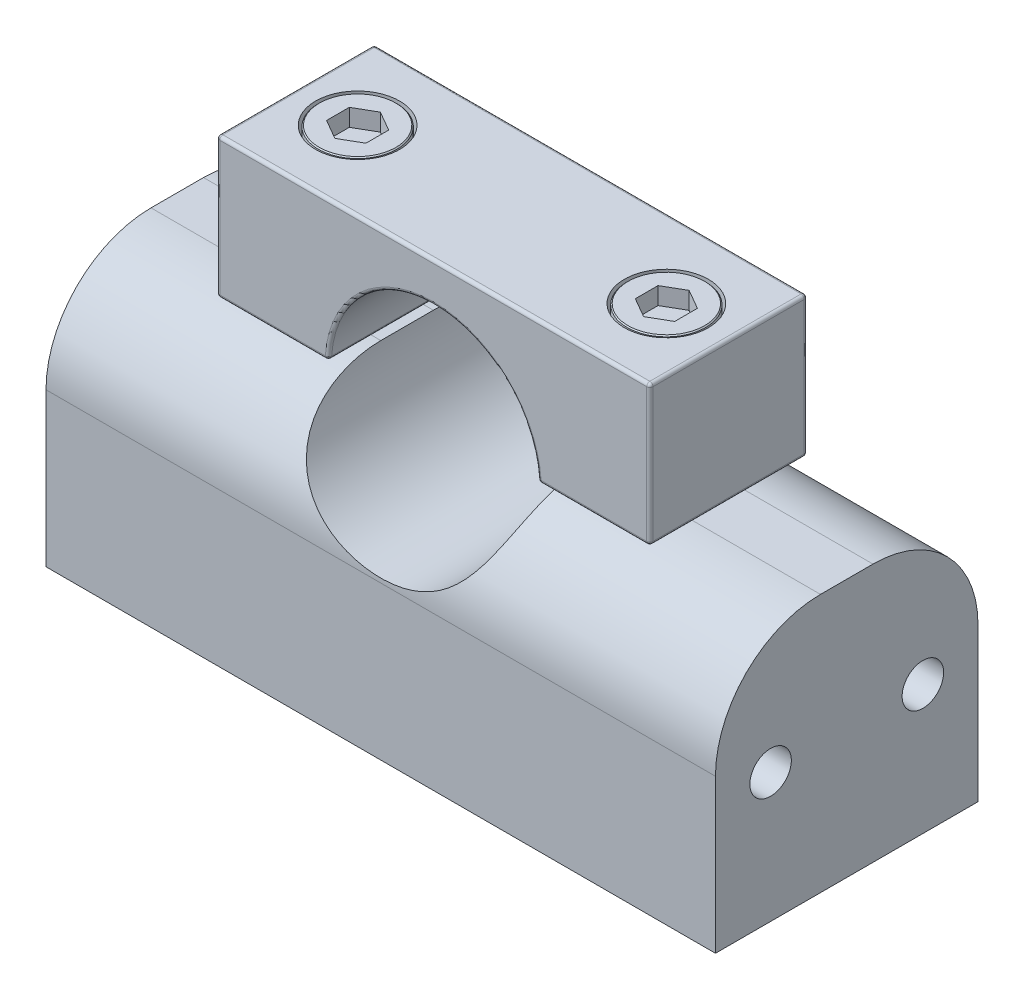
SolidWorks part; units mm, degrees
ref_plane "Front" through (0, 0, 0) normal (0, 0, 1) x (1, 0, 0)
ref_plane "Top" through (0, 0, 0) normal (0, 1, 0) x (1, 0, 0)
ref_plane "Right" through (0, 0, 0) normal (1, 0, 0) x (0, 0, -1)
sketch "Sketch1" plane through (0, 0, 0) normal (0, 0, 1) x (1, 0, 0)
  line L0 (0, 49.2125) -> (0, 0) construction
  line L1 (-40.4812, 0) -> (40.4812, 0) construction
  line L2 (0, 0) -> (0, 31.75) construction
  line L3 (-33.3375, 0) -> (33.3375, 0) construction
  line L4 (29.7815, 0) -> (36.8935, 0) construction
  line L5 (36.8935, 0) -> (36.8935, 1.27) construction
  line L6 (29.7815, 0) -> (29.7815, 1.27) construction
  line L7 (-29.7815, 0) -> (-29.7815, 1.27) construction
  line L8 (-36.8935, 0) -> (-36.8935, 1.27) construction
  line L9 (-29.7815, 0) -> (-36.8935, 0) construction
  line L10 (-26.1938, 31.75) -> (26.1938, 31.75) construction
  line L11 (-26.1937, 31.242) -> (26.1937, 31.242) construction
  line L12 (-26.1937, 32.258) -> (26.1937, 32.258) construction
  line L13 (29.4005, 0) -> (29.4005, 1.27) construction
  line L14 (37.2745, 0) -> (37.2745, 1.27) construction
  line L15 (-29.4005, 0) -> (-29.4005, 1.27) construction
  line L16 (-37.2745, 0) -> (-37.2745, 1.27) construction
  line L17 (-11.0713, 31.242) -> (11.0713, 31.242) construction
  line L18 (-11.0713, 32.258) -> (11.0713, 32.258) construction
  line L19 (-11.0713, 31.75) -> (11.0713, 31.75) construction
  line L20 (-40.4812, 0) -> (-40.4812, 9.8425) construction
  line L21 (-40.4812, 9.8425) -> (-26.1938, 9.8425) construction
  line L22 (-26.1937, 31.242) -> (-26.1938, 9.8425) construction
  line L23 (-26.1937, 32.258) -> (-26.1937, 49.2125) construction
  line L24 (-26.1937, 49.2125) -> (26.1937, 49.2125) construction
  line L25 (40.4812, 0) -> (40.4812, 9.8425) construction
  line L26 (40.4812, 9.8425) -> (26.1938, 9.8425) construction
  line L27 (26.1937, 31.242) -> (26.1938, 9.8425) construction
  line L28 (26.1937, 32.258) -> (26.1937, 49.2125) construction
  line L29 (0, 49.2125) -> (0, 42.8625) construction
  line L30 (0.3175, 42.8625) -> (-0.3175, 42.8625) construction
  line L31 (26.1938, 9.8425) -> (26.1938, 0) construction
  line L32 (-33.3375, 0) -> (-33.3375, 9.8425) construction
  line L33 (0, 44.45) -> (26.1937, 44.45) construction
  line L34 (0, 24.6062) -> (26.1937, 24.6062) construction
  circle A0 centre (0, 31.75) radius 12.7 construction
  arc A1 (-28.0988, 9.8425) -> (-26.1937, 11.7475) centre (-28.0988, 11.7475) ccw construction
  arc A2 (28.0988, 9.8425) -> (26.1937, 11.7475) centre (28.0988, 11.7475) cw construction
  point P5 (0, 0)
  point P9 (0, 31.75)
  point P11 (0, 0)
  point P12 (33.3375, 0)
  point P13 (-33.3375, 0)
  point P16 (33.3375, 0)
  point P37 (0, 31.242)
  point P40 (0, 32.258)
  point P60 (0, 42.8625)
  point P64 (33.3375, 9.8425)
  dimension "D1" = 1.27
  dimension "D8" = 9.8425
  dimension "D12" = 0.635
  dimension "D10" = 1.905
  dimension "D11" = 1.905
  dimension "D9" = 7.1437
  dimension "D3" = 0.508
  dimension "D4" = 0.381
  dimension "D5" = 0.381
  dimension "D6" = 0.381
  dimension "D7" = 0.381
sketch "Sketch3" plane through (0, 0, 0) normal (0, 0, 1) x (1, 0, 0)
  line L0 (-26.1937, 49.2125) -> (26.1937, 49.2125) construction
  line L1 (26.1937, 32.258) -> (26.1937, 49.2125) construction
  line L2 (-26.1937, 32.258) -> (26.1937, 32.258) construction
  line L3 (-26.1937, 32.258) -> (-26.1937, 49.2125) construction
  line L6 (-40.4812, 0) -> (-40.4812, 9.8425) construction
  line L7 (-40.4812, 0) -> (40.4812, 0) construction
  line L8 (40.4812, 0) -> (40.4812, 9.8425) construction
  line L11 (-26.1937, 31.242) -> (26.1937, 31.242) construction
  line L12 (-26.1937, 49.2125) -> (26.1937, 49.2125)
  line L13 (26.1937, 32.258) -> (26.1937, 49.2125)
  line L14 (-26.1937, 32.258) -> (-12.6898, 32.258)
  line L15 (-26.1937, 32.258) -> (-26.1937, 49.2125)
  line L18 (-40.4812, 0) -> (-40.4812, 9.8425)
  line L19 (-40.4812, 0) -> (40.4812, 0)
  line L20 (40.4812, 0) -> (40.4812, 9.8425)
  line L23 (-26.1937, 31.242) -> (-12.6898, 31.242)
  line L24 (12.6898, 32.258) -> (26.1937, 32.258)
  line L25 (12.6898, 31.242) -> (26.1937, 31.242)
  line L26 (-40.4812, 9.8425) -> (-40.4812, 31.242)
  line L27 (-40.4812, 31.242) -> (-26.1937, 31.242)
  line L28 (40.4812, 9.8425) -> (40.4812, 31.242)
  line L29 (40.4812, 31.242) -> (26.1937, 31.242)
  circle A2 centre (0, 31.75) radius 12.7 construction
  arc A5 (12.6898, 32.258) -> (-12.6898, 32.258) centre (0, 31.75) ccw
  arc A6 (-12.6898, 31.242) -> (12.6898, 31.242) centre (0, 31.75) ccw
extrude "Boss-Extrude1" add sketch "Sketch3" against normal blind 19.05
sketch "Sketch4" plane through (0, 0, 0) normal (0, -1, 0) x (1, 0, 0)
  line L0 (-40.4813, 0) -> (-40.4812, -19.05) construction
  line L1 (-40.4812, 0) -> (-26.1937, 0) construction
  line L2 (-40.4812, -9.525) -> (40.4812, -9.525) construction
  line L3 (40.4812, -19.05) -> (40.4812, 0) construction
  line L4 (-33.3375, 0) -> (-33.3375, -19.05) construction
  line L5 (33.3375, 0) -> (33.3375, -19.05) construction
  line L6 (-40.4812, -19.05) -> (40.4812, -19.05) construction
  line L7 (0, 0) -> (0, -19.05) construction
  circle A0 centre (-33.3375, -9.525) radius 3.556
  circle A1 centre (33.3375, -9.525) radius 3.556
  point P7 (-40.4812, -9.525)
  dimension "D1" = 7.112
sketch "Sketch6" plane through (0, 9.8425, 0) normal (0, 1, 0) x (1, 0, 0)
  line L0 (0, 0) -> (0, 19.05) construction
  line L1 (-40.4813, 0) -> (40.4812, 0) construction
  line L2 (26.1937, 19.05) -> (-26.1937, 19.05) construction
  circle A1 centre (-33.3375, 9.525) radius 3.556 construction
  circle A2 centre (-33.3375, 9.525) radius 3.556
  circle A4 centre (-33.3375, 9.525) radius 3.937
  circle A5 centre (33.3375, 9.525) radius 3.937
  dimension "D1" = 0.381
sketch "Sketch7" plane through (0, 0, 0) normal (0, 0, 1) x (1, 0, 0)
  line L0 (-40.4812, 9.5885) -> (40.4812, 9.5885) construction
  line L1 (-26.1937, 31.242) -> (-26.1937, 0) construction
  line L2 (-40.4812, 0) -> (40.4812, 0) construction
  line L3 (26.1937, 31.242) -> (26.1937, 0) construction
  line L5 (-40.4812, 0) -> (-40.4812, 9.8425) construction
  line L6 (-40.4812, 9.8425) -> (-26.1938, 9.8425) construction
  line L7 (40.4812, 0) -> (40.4812, 9.8425) construction
  line L8 (-33.3375, 9.8425) -> (-33.3375, 9.5885) construction
  line L9 (33.3375, 9.8425) -> (33.3375, 9.5885) construction
  line L10 (40.4812, 9.8425) -> (26.1938, 9.8425) construction
  dimension "D1" = 0.254
sketch "Sketch8" plane through (0, 31.242, 0) normal (0, 1, 0) x (1, 0, 0)
  line L0 (0, 0) -> (0, 19.05) construction
  line L1 (26.1938, 19.05) -> (-26.1937, 19.05) construction
  circle A0 centre (-33.3375, 9.525) radius 3.937 construction
  circle A1 centre (33.3375, 9.525) radius 3.937 construction
  circle A2 centre (-33.3375, 9.525) radius 3.937 construction
  circle A3 centre (33.3375, 9.525) radius 3.937 construction
  circle A4 centre (-33.3375, 9.525) radius 4.318
  circle A5 centre (33.3375, 9.525) radius 4.318
  dimension "CounterBoreID" = 8.636
sketch "Sketch10" plane through (0, 49.2125, 0) normal (0, 1, 0) x (1, 0, 0)
  line L0 (-26.1937, 19.05) -> (-26.1937, 0) construction
  line L1 (26.1937, 19.05) -> (26.1937, 0) construction
  line L2 (-26.1937, 19.05) -> (-26.1937, 0) construction
  line L3 (26.1937, 19.05) -> (26.1937, 0) construction
  line L4 (-23.4315, 19.05) -> (-23.4315, 0) construction
  line L5 (0, 0) -> (0, 19.05) construction
  line L6 (23.4315, 19.05) -> (23.4315, 0) construction
  circle A0 centre (-18.669, 9.525) radius 3.175 construction
  circle A1 centre (18.669, 9.525) radius 3.429
  circle A2 centre (-18.669, 9.525) radius 3.429
  circle A3 centre (18.669, 9.525) radius 3.175 construction
  circle A4 centre (-18.669, 9.525) radius 4.7625 construction
  circle A5 centre (18.669, 9.525) radius 4.7625 construction
extrude "Cut-Extrude4" cut sketch "Sketch10" against normal through all
ref_plane "Plane1" through (0, 0, -9.525) normal (0, 0, 1) x (1, 0, 0)
sketch "Sketch12" plane through (0, 49.2125, 0) normal (0, 1, 0) x (1, 0, 0)
  line L0 (0, 19.05) -> (0, 0) construction
  circle A0 centre (-18.669, 9.525) radius 4.953 construction
  circle A1 centre (18.669, 9.525) radius 5.08
  circle A2 centre (-18.669, 9.525) radius 5.08
  circle A3 centre (18.669, 9.525) radius 4.953 construction
  dimension "D2" = 10.16
  dimension "D1" = 0.127
extrude "Cut-Extrude5" cut sketch "Sketch12" against normal blind 6.731
sketch "Sketch13" plane through (0, 0, 0) normal (0, 1, 0) x (1, 0, 0)
  line L0 (-18.669, 19.05) -> (-18.669, 0) construction
  line L1 (26.1937, 19.05) -> (-26.1937, 19.05) construction
  line L2 (0, 19.05) -> (0, 0) construction
  line L3 (18.669, 19.05) -> (18.669, 0) construction
  circle A0 centre (-18.669, 9.525) radius 2.0066 construction
  point P2 (-18.669, 9.525)
  point P9 (-18.669, 19.05)
  point P10 (-18.669, 0)
  point P17 (18.669, 19.05)
  point P18 (18.669, 0)
  dimension "D1" = 4.0132
sketch "Sketch15" plane through (0, 0, -9.525) normal (0, 0, 1) x (1, 0, 0)
  line L0 (-18.669, 19.685) -> (-18.669, 49.2125) construction
  line L1 (-18.669, 49.2125) -> (-23.4315, 49.2125) construction
  line L2 (-23.4315, 49.2125) -> (-23.4315, 42.8625) construction
  line L3 (-23.4315, 42.8625) -> (-21.844, 42.8625) construction
  line L4 (-21.844, 42.8625) -> (-21.844, 19.685) construction
  line L5 (-21.844, 19.685) -> (-18.669, 19.685) construction
  line L8 (-26.1937, 49.2125) -> (26.1937, 49.2125) construction
  line L9 (-18.669, 19.685) -> (-18.669, 49.2125)
  line L10 (-18.669, 49.2125) -> (-23.4315, 49.2125)
  line L11 (-23.4315, 49.2125) -> (-23.4315, 42.8625)
  line L12 (-23.4315, 42.8625) -> (-21.844, 42.8625)
  line L13 (-21.844, 42.8625) -> (-21.844, 19.685)
  line L14 (-21.844, 19.685) -> (-18.669, 19.685)
  dimension "D2" = 4.7625
  dimension "D1" = 6.35
  dimension "D3" = 3.175
  dimension "Screw Length" = 29.5275
revolve "Revolve1" add sketch "Sketch15" angle 360 about L9
chamfer "Chamfer1" distance 0.127 angle 45 1 edges at (-18.669, 49.2125, -14.2875)
sketch "Sketch16" plane through (0, 49.2125, 0) normal (0, 1, 0) x (1, 0, 0)
  line L0 (-18.669, 19.05) -> (-18.669, 0) construction
  line L1 (-18.669, 12.2746) -> (-21.0502, 10.8998)
  line L2 (-21.0502, 10.8998) -> (-21.0502, 8.1502)
  line L3 (-21.0502, 8.1502) -> (-18.669, 6.7754)
  line L4 (-18.669, 6.7754) -> (-16.2877, 8.1502)
  line L5 (-16.2877, 8.1502) -> (-16.2877, 10.8998)
  line L6 (-16.2877, 10.8998) -> (-18.669, 12.2746)
  circle A0 centre (-18.669, 9.525) radius 2.3813 construction
  dimension "Hex Size" = 4.7625
extrude "Cut-Extrude6" cut sketch "Sketch16" against normal blind 2.0955
mirror "Mirror1" about plane through (0, 0, 0) normal (1, 0, 0) of bodies 121 119
fillet "Fillet1" radius 0.381 18 edges at (0, 49.2125, -19.05) (-26.1937, 49.2125, -9.525) (-26.1937, 40.7353, -19.05) (-26.1937, 40.7353, 0) (26.1937, 40.7353, -19.05) (26.1937, 49.2125, -9.525) (26.1937, 40.7353, 0) (0, 49.2125, 0) (26.1937, 32.258, -9.525) (19.4418, 32.258, -19.05) (-19.4418, 32.258, -19.05) (-26.1937, 32.258, -9.525) (-19.4418, 32.258, 0) (19.4418, 32.258, 0) (0, 44.45, -19.05) (0, 44.45, 0) (12.6898, 32.258, -9.525) (-12.6898, 32.258, -9.525)
ref_plane "Contact Plane 1" through (0, 0, -9.525) normal (0, 0, -1) x (-1, 0, 0)
ref_plane "Contact Plane 2" through (0, 0, 0) normal (-1, 0, 0) x (0, 0, 1)
ref_plane "Contact Plane 3" through (0, 24.6063, 0) normal (0, 1, 0) x (1, 0, 0)
ref_plane "Contact Plane 4" through (0, 49.2125, 0) normal (0, 1, 0) x (1, 0, 0)
ref_plane "Contact Plane 5" through (0, 0, 0) normal (0, -1, 0) x (-1, 0, 0)
ref_plane "Contact Plane 6" through (40.4812, 0, 0) normal (1, 0, 0) x (0, 0, -1)
ref_plane "Contact Plane 7" through (-40.4812, 0, 0) normal (-1, 0, 0) x (0, 0, 1)
ref_axis "Center Axis 1" through (0, 54.8037, -9.525) along (0, -1, 0)
ref_axis "Center Axis 2" through (0, 24.6063, -33.3184) along (0, 0, 1)
ref_axis "Center Axis 3" through (69.4309, 24.6063, -9.525) along (-1, 0, 0)
sketch "Sketch17" plane through (0, 0, 0) normal (0, 0, 1) x (1, 0, 0)
  line L5 (-12.6898, 31.242) -> (-40.4812, 31.242)
  line L6 (-40.4812, 31.242) -> (-40.4812, 0)
  line L7 (-40.4812, 0) -> (40.4812, 0)
  line L8 (40.4812, 0) -> (40.4812, 31.242)
  line L9 (40.4812, 31.242) -> (12.6898, 31.242)
  line L10 (-12.6898, 31.242) -> (-40.4812, 31.242)
  line L11 (-40.4812, 31.242) -> (-40.4812, 0)
  line L12 (-40.4812, 0) -> (40.4812, 0)
  line L13 (40.4812, 0) -> (40.4812, 31.242)
  line L14 (40.4812, 31.242) -> (12.6898, 31.242)
  arc A1 (-12.6898, 31.242) -> (12.6898, 31.242) centre (0, 31.75) ccw
  arc A2 (-12.6898, 31.242) -> (12.6898, 31.242) centre (0, 31.75) ccw
  dimension "D1" = 0
extrude "Boss-Extrude2" add sketch "Sketch17" along normal blind 6.35
extrude "Boss-Extrude3" add sketch "Sketch17<2>" against normal blind 6.35 from surface starting at face at (0, 18.796, -19.05)
sketch "Sketch17<2>" plane through (0, 0, 0) normal (0, 0, 1) x (1, 0, 0) same geometry as "Sketch17"
sketch "Sketch18" plane through (-40.4812, 0, 0) normal (-1, 0, 0) x (0, 0, 1)
  line L0 (-9.525, 48.8315) -> (-9.525, 0) construction
  line L1 (-25.4, 0) -> (6.35, 0) construction
  line L2 (-12.065, 48.8315) -> (-12.065, 31.242) construction
  line L3 (-12.065, 31.242) -> (-12.065, 0) construction
  line L4 (-25.4, 31.242) -> (6.35, 31.242) construction
  line L5 (-12.065, 15.621) -> (-25.4, 15.621) construction
  line L6 (-25.4, 31.242) -> (-25.4, 0) construction
  line L7 (-0.381, 48.8315) -> (-18.669, 48.8315) construction
  circle A0 centre (-18.7325, 15.621) radius 2.5082
  circle A2 centre (-0.3175, 15.621) radius 2.5082
  dimension "D1" = 5.0165
  dimension "D2" = 2.54
extrude "Cut-Extrude7" cut sketch "Sketch18" against normal up to surface (80.9625 mm away) up to face at (40.4812, 15.621, -9.525)
fillet "Fillet2" radius 12.7 2 edges at (-26.5855, 31.242, 6.35) (-26.5855, 31.242, -25.4)
equation "\"D8@Sketch1\"=\"Oall Ht@Sketch1\"*.20"
equation "\"D1@Sketch4\"= \"HoldDia@Sketch1\""
equation "\"D1@Cut-Extrude5\"=\"HeadDp@Sketch1\"+.015"
equation "\"D1@Sketch15\"=\"HeadDp@Sketch1\""
equation "\"D3@Sketch15\"=\"ThrdDia@Sketch10\"*.5"
equation "\"D1@Cut-Extrude6\"= \"HeadDp@Sketch1\"*.33"
equation "\"D2@Sketch12\"=\"Head Dia@Sketch10\"+.025"
equation "\"D2@Sketch15\"=\"Head Dia@Sketch10\"*.50"
